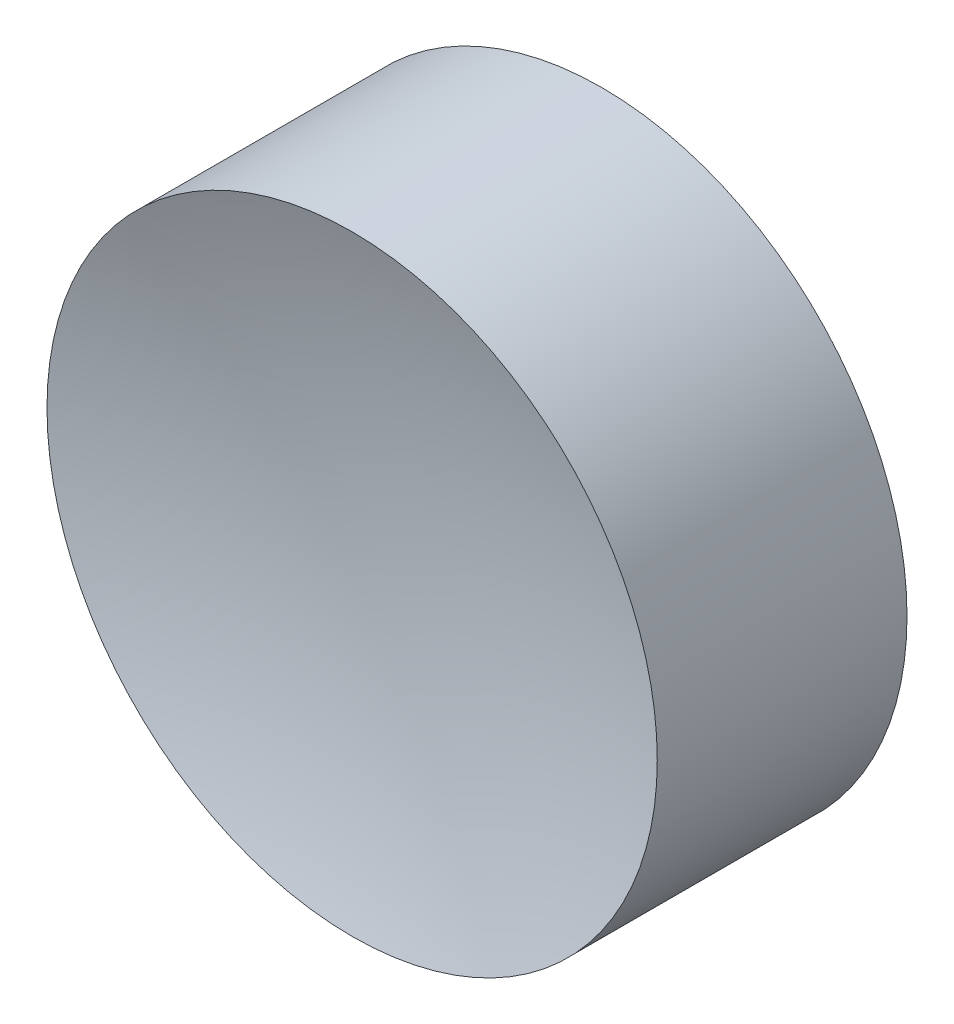
SolidWorks part; units mm, degrees
ref_plane "Ebene vorne" through (0, 0, 0) normal (0, 0, 1) x (1, 0, 0)
ref_plane "Ebene oben" through (0, 0, 0) normal (0, 1, 0) x (1, 0, 0)
ref_plane "Ebene rechts" through (0, 0, 0) normal (1, 0, 0) x (0, 0, -1)
other "Massenmittelpunkt"
sketch "Skizze1" plane through (0, 0, 0) normal (0, 1, 0) x (1, 0, 0)
  line L0 (0, 0.75) -> (0, -0.75)
  line L1 (3, -1.2276) -> (3, 1.2276)
  line L2 (0, 1.2276) -> (0, -1.2276) construction
  arc A0 (3, 1.2276) -> (0, 0.75) centre (0, 10.41) cw
  arc A1 (0, -0.75) -> (3, -1.2276) centre (0, -10.41) cw
revolve "Rotation1" add sketch "Skizze1" angle 360 about L2 reverse direction yes
ref_plane "Ebene1" through (3, 0, 0) normal (1, 0, 0) x (0, 0, -1)
ref_axis "Achse2" through (-3.3, 0, 0) along (1, 0, 0)
ref_point "Punkt1"
ref_axis "Opitcal_Axis" through (0, 0, -1.2276) along (0, 0, 1)
ref_plane "Ebene2" through (-3, 0, 0) normal (-1, 0, 0) x (0, 0, 1)
ref_point "Punkt2"
ref_point "Punkt3"
